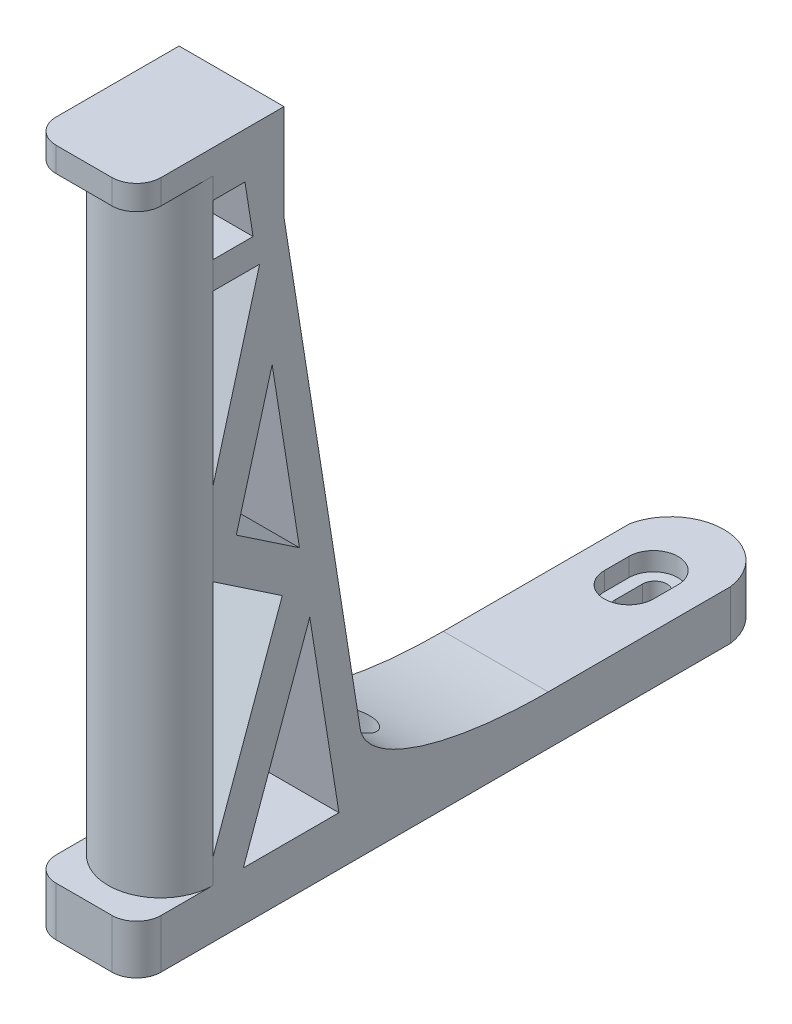
SolidWorks part; units mm, degrees
note: The reader was unsure of these and kept them because the rebuilt part matched: shared geometry of "Sketch1<3>", "Sketch1<4>", "Sketch1<5>", "Sketch1<6>", "Sketch4<2>".
ref_plane "Front" through (0, 0, 0) normal (0, 0, 1) x (1, 0, 0)
ref_plane "Top" through (0, 0, 0) normal (0, 1, 0) x (1, 0, 0)
ref_plane "Right" through (0, 0, 0) normal (1, 0, 0) x (0, 0, -1)
sketch "Sketch1" plane through (0, 0, 0) normal (0, 1, 0) x (1, 0, 0)
  line L0 (-76.1695, -162.2157) -> (-76.1695, -112.0048) construction
  line L1 (-106.175, -137.1103) -> (-46.1639, -137.1103) construction
  line L2 (-67.6317, -178.6668) -> (-84.7072, -178.6668)
  line L5 (-76.1695, -160.2157) -> (-76.1695, -164.2157) construction
  line L6 (-72.1695, -160.2157) -> (-72.1695, -164.2157)
  line L7 (-80.1695, -160.2157) -> (-80.1695, -164.2157)
  line L8 (-76.1695, -114.0048) -> (-76.1735, -110.0048) construction
  line L9 (-76.1695, -114.0048) -> (-76.1735, -110.0048) construction
  line L10 (-76.1695, -110.0048) -> (-76.1695, -114.0048) construction
  line L11 (-72.1695, -110.0048) -> (-72.1695, -114.0048)
  line L12 (-80.1695, -110.0048) -> (-80.1695, -114.0048)
  line L13 (-84.7072, -105.2951) -> (-84.7072, -190.2157)
  line L14 (-67.6317, -106.0048) -> (-67.6317, -190.2157)
  line L15 (-84.7072, -190.2157) -> (-67.6317, -190.2157) construction
  line L38 (-76.1695, -114.2157) -> (-76.1695, -109.794) construction
  line L39 (-78.1695, -114.2157) -> (-78.1695, -109.794)
  line L40 (-74.1695, -114.2157) -> (-74.1695, -109.794)
  line L41 (-76.1695, -164.2157) -> (-76.1695, -160.294) construction
  line L42 (-78.1695, -164.2157) -> (-78.1695, -160.294)
  line L43 (-74.1695, -164.2157) -> (-74.1695, -160.294)
  arc A0 (-84.7072, -105.2951) -> (-67.6317, -106.0048) centre (-76.2316, -107.1444) cw
  arc A2 (-72.1695, -160.2157) -> (-80.1695, -160.2157) centre (-76.1695, -160.2157) ccw
  arc A3 (-80.1695, -164.2157) -> (-72.1695, -164.2157) centre (-76.1695, -164.2157) ccw
  arc A4 (-72.1695, -110.0048) -> (-80.1695, -110.0048) centre (-76.1695, -110.0048) ccw
  arc A5 (-80.1695, -114.0048) -> (-72.1695, -114.0048) centre (-76.1695, -114.0048) ccw
  arc A7 (-84.7072, -190.2157) -> (-67.6317, -190.2157) centre (-76.1695, -190.2157) ccw
  circle A12 centre (-76.1695, -114.2157) radius 2 construction
  circle A13 centre (-76.1695, -164.2157) radius 2 construction
  arc A20 (-78.1695, -114.2157) -> (-74.1695, -114.2157) centre (-76.1695, -114.2157) ccw
  arc A21 (-74.1695, -109.794) -> (-78.1695, -109.794) centre (-76.1695, -109.794) ccw
  arc A23 (-78.1695, -164.2157) -> (-74.1695, -164.2157) centre (-76.1695, -164.2157) ccw
  arc A24 (-74.1695, -160.294) -> (-78.1695, -160.294) centre (-76.1695, -160.294) ccw
  point P3 (-76.1695, -162.2548)
  point P6 (-76.1695, -137.1103)
  point P14 (-76.1695, -162.2157)
  point P22 (-76.1695, -112.0048)
  point P65 (-76.1695, -112.0048)
  point P73 (-76.1695, -162.2548)
  dimension "D2" = 112.0048
  dimension "D5" = 4
  dimension "D12" = 2
  dimension "D13" = 2
  dimension "D33" = 2
  dimension "D4" = 4
  dimension "D6" = 26
  dimension "D16" = 50
extrude "Boss-Extrude1" add sketch "Sketch1" along normal blind 5 contours L13 A7 L14 L2 | A0 L13 L2 L14 A5 L12 A4 L11 A3 L7 A2 L6 | L7 A3 L6 A2 A24 L43 A23 L42 | L12 A5 L11 A4 A21 L40 A20 L39 | L43 A24 L42 A23
extrude "Boss-Extrude2" add sketch "Sketch1<3>" along normal blind 3 from vertex
sketch "Sketch1<3>" plane through (0, 0, 0) normal (0, 1, 0) x (1, 0, 0) same geometry as "Sketch1"
extrude "Boss-Extrude3" add sketch "Sketch1<4>" along normal blind 100 from vertex contours L13 A7 L14 L2
sketch "Sketch1<4>" plane through (0, 0, 0) normal (0, 1, 0) x (1, 0, 0) same geometry as "Sketch1"
chamfer "Chamfer1" distance 14 angle 81 1 edges
fillet "Fillet1" radius 15 1 edges at (-76.1695, 8, 164.6668)
sketch "Sketch2" plane through (-84.7072, 0, 0) normal (-1, 0, 0) x (0, 0, 1)
  line L0 (182.6361, 91.7691) -> (190.2157, 91.7691)
  line L1 (190.2157, 91.7691) -> (190.2157, 12.0258)
  line L2 (185.2906, 8) -> (169.7291, 8)
  line L3 (169.7291, 8) -> (174.4715, 37.9424)
  line L4 (178.6668, 96.3925) -> (166.2744, 18.1505) construction
  line L5 (105.2951, 8) -> (135.6561, 8) construction
  line L6 (178.9463, 43.2141) -> (193.362, 52.912) construction
  line L7 (185.2906, 70.8778) -> (181.7306, 83.7748)
  line L8 (189.8955, 54.1956) -> (181.7306, 83.7748) construction
  line L9 (186.429, 55.4793) -> (180.596, 76.6108)
  line L10 (176.1543, 48.5672) -> (186.429, 55.4793)
  line L11 (174.4715, 37.9424) -> (185.2906, 8)
  line L12 (190.2157, 64.3104) -> (182.6361, 91.7691)
  line L13 (178.9463, 43.2141) -> (190.2157, 50.7953)
  line L14 (178.9463, 43.2141) -> (190.2157, 12.0258)
  line L15 (193.362, 52.912) -> (184.6225, 84.5731) construction
  line L16 (171.7122, 45.5788) -> (186.429, 55.4793) construction
  line L17 (171.7122, 45.5788) -> (184.8735, 9.1545) construction
  line L18 (175.3293, 44.3965) -> (189.8955, 54.1956) construction
  line L19 (175.3293, 44.3965) -> (187.6949, 10.174) construction
  line L20 (186.429, 55.4793) -> (178.8388, 82.9765) construction
  line L21 (178.9463, 43.2141) -> (190.5164, 11.1935) construction
  line L22 (176.1543, 48.5672) -> (180.596, 76.6108)
  line L24 (190.2157, 96.1999) -> (190.2157, 104.5542)
  line L25 (178.6668, 108) -> (190.2157, 108) construction
  line L26 (190.2157, 104.5542) -> (185.0218, 104.5542)
  line L27 (185.0218, 104.5542) -> (183.6986, 96.1999)
  line L28 (183.6986, 96.1999) -> (190.2157, 96.1999)
  line L29 (190.2157, 108) -> (190.2157, 0) construction
  dimension "D3" = 5
  dimension "D5" = 16.2309
  dimension "D1" = 3
  dimension "D2" = 3
extrude "Cut-Extrude1" cut sketch "Sketch2" against normal up to next
extrude "Cut-Extrude2" cut sketch "Sketch1<5>" along normal up to next contours L43 A24 L42 A23
sketch "Sketch1<5>" plane through (0, 0, 0) normal (0, 1, 0) x (1, 0, 0) same geometry as "Sketch1"
extrude "Cut-Extrude3" cut sketch "Sketch1<6>" along normal up to next from vertex contours L7 A3 L6 A2 A24 L43 A23 L42
sketch "Sketch1<6>" plane through (0, 0, 0) normal (0, 1, 0) x (1, 0, 0) same geometry as "Sketch1"
sketch "Sketch4" plane through (0, 108, 0) normal (0, 1, 0) x (1, 0, 0)
  line L0 (-67.6317, -178.6668) -> (-67.6317, -198.6668)
  line L1 (-71.6317, -202.6668) -> (-80.7072, -202.6668)
  line L2 (-84.7072, -198.6668) -> (-84.7072, -178.6668)
  line L3 (-84.7072, -178.6668) -> (-67.6317, -178.6668)
  arc A0 (-80.7072, -202.6668) -> (-84.7072, -198.6668) centre (-80.7072, -198.6668) cw
  arc A1 (-67.6317, -198.6668) -> (-71.6317, -202.6668) centre (-71.6317, -198.6668) cw
  dimension "D1" = 4
  dimension "D2" = 24
extrude "Boss-Extrude4" add sketch "Sketch4" along normal blind 4
extrude "Boss-Extrude5" add sketch "Sketch4<2>" along normal up to vertex from vertex
sketch "Sketch4<2>" plane through (0, 108, 0) normal (0, 1, 0) x (1, 0, 0) same geometry as "Sketch4"
ref_plane "Plane1" through (0, -36.2802, 13.1092) normal (0, 0.9405, -0.3398) x (1, 0, 0)
sketch "Sketch5" plane through (0, -36.2802, 13.1092) normal (0, 0.9405, -0.3398) x (1, 0, 0)
  line L0 (-67.6317, -162.5471) -> (-67.6317, -200.7908) construction
  line L1 (-71.6317, -170.3467) -> (-80.7072, -170.3467)
  line L2 (-71.6317, -170.3467) -> (-71.6317, -168.9821)
  line L3 (-71.6317, -168.9821) -> (-80.7072, -168.9821)
  line L4 (-80.7072, -170.3467) -> (-80.7072, -168.9821)
  line L5 (-71.6317, -170.3467) -> (-80.7072, -168.9821) construction
  line L6 (-71.6317, -168.9821) -> (-80.7072, -170.3467) construction
  line L7 (-84.7072, -200.7908) -> (-84.7072, -162.5471) construction
  line L9 (-67.6317, -176.9821) -> (-84.7072, -176.9821) construction
  line L10 (-67.6317, -162.3467) -> (-84.7072, -162.3467) construction
  point P0 (-76.1695, -169.6644)
  point P9 (-76.1695, -176.9821)
  dimension "D1" = 4
  dimension "D2" = 4
  dimension "D3" = 8
  dimension "D4" = 8
